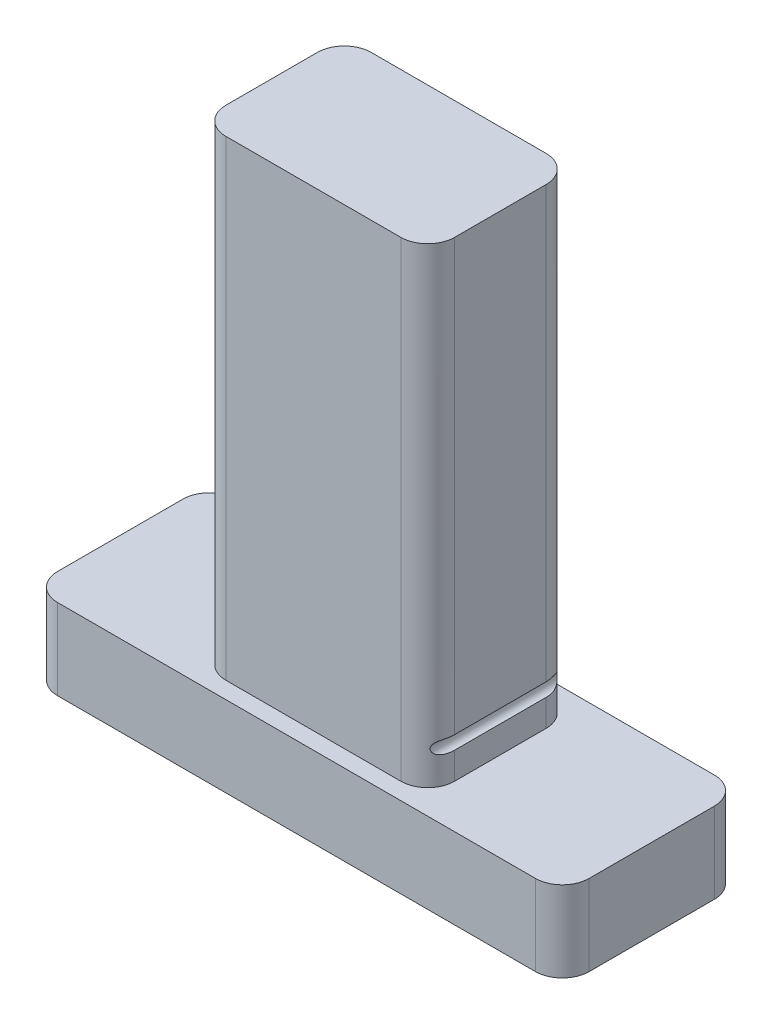
SolidWorks part; units mm, degrees
ref_plane "Front Plane" through (0, 0, 0) normal (0, 0, 1) x (1, 0, 0)
ref_plane "Top Plane" through (0, 0, 0) normal (0, 1, 0) x (1, 0, 0)
ref_plane "Right Plane" through (0, 0, 0) normal (1, 0, 0) x (0, 0, -1)
sketch "Sketch2" plane through (0, 0, 0) normal (0, 1, 0) x (1, 0, 0)
  line L1 (-35.5, 11.3) -> (35.5, 11.3)
  line L2 (-37.5, 9.3) -> (-37.5, -9.3)
  line L3 (-35.5, -11.3) -> (35.5, -11.3)
  line L4 (37.5, 9.3) -> (37.5, -9.3)
  line L5 (-37.5, 11.3) -> (37.5, -11.3) construction
  line L6 (-37.5, -11.3) -> (37.5, 11.3) construction
  arc A0 (35.5, 11.3) -> (37.5, 9.3) centre (35.5, 9.3) cw
  arc A1 (37.5, -9.3) -> (35.5, -11.3) centre (35.5, -9.3) cw
  arc A2 (-35.5, -11.3) -> (-37.5, -9.3) centre (-35.5, -9.3) cw
  arc A3 (-37.5, 9.3) -> (-35.5, 11.3) centre (-35.5, 9.3) cw
  point P4 (0, 0)
  point P5 (23.7796, -17.7518)
  point P6 (0, 0)
  dimension "D3" = 2
  dimension "D1" = 22.6
  dimension "D2" = 75
extrude "Boss-Extrude1" add sketch "Sketch2" along normal blind 10
sketch "Sketch3" plane through (0, 10, 0) normal (0, 1, 0) x (1, 0, 0)
  line L0 (-35.5, -11.3) -> (35.5, -11.3) construction
  line L1 (-13, -8.8) -> (13, -8.8)
  line L2 (-15, -6.8) -> (-15, 6.8)
  line L3 (-13, 8.8) -> (13, 8.8)
  line L4 (15, -6.8) -> (15, 6.8)
  line L5 (-15, -8.8) -> (15, 8.8) construction
  line L6 (-15, 8.8) -> (15, -8.8) construction
  arc A0 (-15, -6.8) -> (-13, -8.8) centre (-13, -6.8) ccw
  arc A1 (13, -8.8) -> (15, -6.8) centre (13, -6.8) ccw
  arc A2 (15, 6.8) -> (13, 8.8) centre (13, 6.8) ccw
  arc A3 (-13, 8.8) -> (-15, 6.8) centre (-13, 6.8) ccw
  point P0 (0, 0)
  dimension "D3" = 2
  dimension "D1" = 2.5
  dimension "D2" = 30
extrude "Boss-Extrude2" add sketch "Sketch3" along normal blind 70
shell "Shell1" thickness 2 removed face at (0, 0, 0) outward yes
sketch "Sketch6" plane through (15, 0, 0) normal (1, 0, 0) x (0, 0, -1)
  line L1 (-8.8, 17) -> (8.8, 17)
  line L2 (-8.8, 17) -> (-8.8, 15)
  line L3 (-8.8, 15) -> (8.8, 15)
  line L4 (8.8, 17) -> (8.8, 15)
  line L5 (-8.8, 17) -> (8.8, 15) construction
  line L6 (-8.8, 15) -> (8.8, 17) construction
  line L9 (-8.8, 80) -> (-8.8, 10) construction
  line L10 (8.8, 80) -> (8.8, 10) construction
  line L11 (-9.3, 12) -> (9.3, 12) construction
  point P4 (0, 16)
  point P5 (9.7504, 16.8781)
  point P6 (0, 0)
  point P7 (-10.8, 25.9764)
  point P8 (-9.1126, 24.0595)
  point P9 (-9.4615, 24.046)
  point P10 (10.8, 18.3626)
  dimension "D1" = 2
  dimension "D2" = 5
revolve "Revolve1" add sketch "Sketch6" angle 180 about L1
sketch "Sketch7" plane through (17, 0, 0) normal (1, 0, 0) x (0, 0, -1)
  line L0 (-8.8, 17) -> (8.8, 17) construction
  line L1 (-10.8, 17) -> (10.8, 17)
  line L2 (-10.8, 17) -> (-10.8, 16)
  line L3 (-10.8, 16) -> (10.8, 16)
  line L4 (10.8, 17) -> (10.8, 16)
  line L5 (-10.8, 17) -> (10.8, 16) construction
  line L6 (-10.8, 16) -> (10.8, 17) construction
  line L8 (-10.8, 82) -> (-10.8, 12) construction
  line L9 (10.8, 82) -> (10.8, 12) construction
  point P4 (0, 16.5)
  dimension "D1" = 1
revolve "Cut-Revolve2" cut sketch "Sketch7" angle 180 about L1
mirror "Mirror2" about plane through (0, 0, 0) normal (1, 0, 0) of "Revolve1", "Cut-Revolve2"
